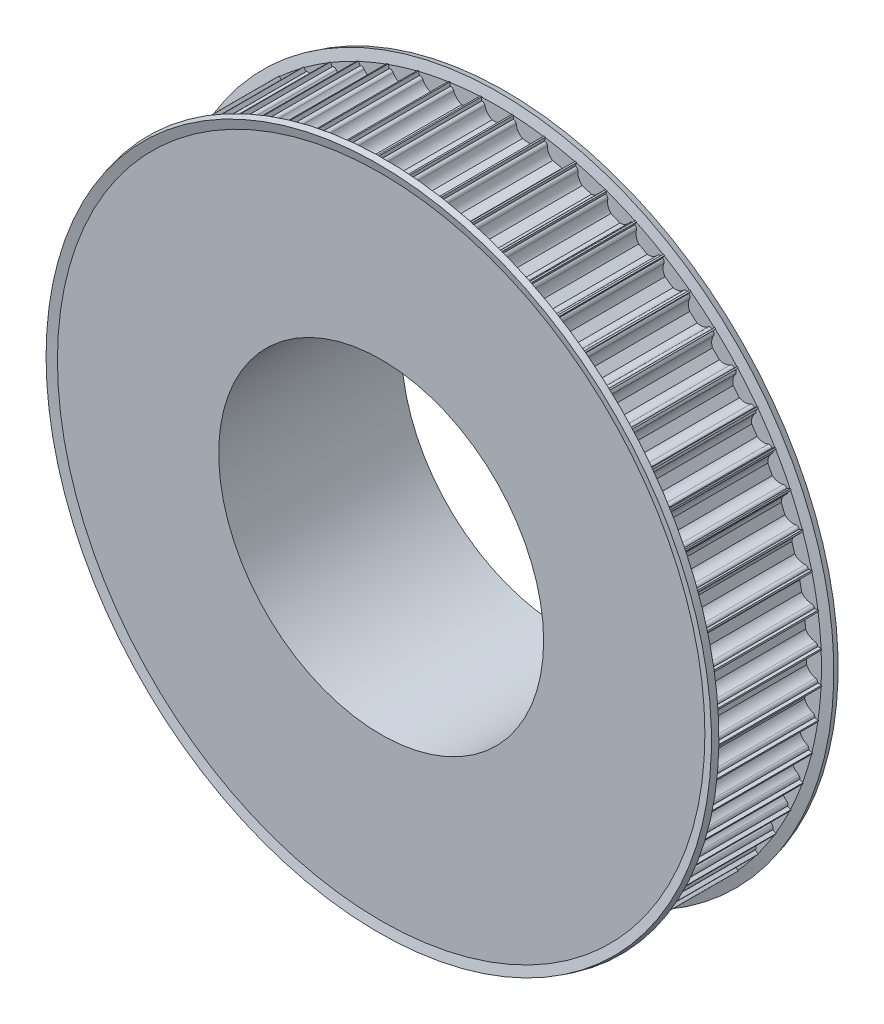
SolidWorks part; units mm, degrees
ref_plane "Front Plane" through (0, 0, 0) normal (0, 0, 1) x (1, 0, 0)
ref_plane "Top Plane" through (0, 0, 0) normal (0, 1, 0) x (1, 0, 0)
ref_plane "Right Plane" through (0, 0, 0) normal (1, 0, 0) x (0, 0, -1)
sketch "Sketch1" plane through (0, 0, 0) normal (1, 0, 0) x (0, 0, -1)
  line L0 (0, 40) -> (45, 40)
  line L1 (45, 40) -> (45, 55.5)
  line L2 (45, 55.5) -> (30, 55.5)
  line L3 (30, 55.5) -> (30, 80)
  line L4 (30, 80) -> (0, 80)
  line L5 (0, 80) -> (0, 40)
  line L6 (0, 0) -> (50000, 0) construction
  dimension "D1" = 30
  dimension "D2" = 40
  dimension "D3" = 15
  dimension "D4" = 40
  dimension "D5" = 15.5
revolve "Revolve1" add sketch "Sketch1" angle 360 about L6
sketch "Sketch2" plane through (0, 0, 0) normal (0, 0, 1) x (1, 0, 0)
  line L1 (3.75, 79) -> (3.6742, 79)
  line L2 (3.75, 79) -> (3.75, 81)
  line L3 (3.75, 81) -> (-3.75, 81)
  line L4 (-3.75, 79) -> (-3.75, 81)
  line L5 (-3.6742, 79) -> (-3.75, 79)
  line L6 (-1.199, 76.25) -> (1.199, 76.25)
  arc A0 (2.9394, 78.4) -> (1.199, 76.25) centre (0, 79) cw
  arc A1 (2.9394, 78.4) -> (3.6742, 79) centre (3.6742, 78.25) cw
  arc A2 (-2.9394, 78.4) -> (-3.6742, 79) centre (-3.6742, 78.25) ccw
  arc A3 (-1.199, 76.25) -> (-2.9394, 78.4) centre (0, 79) cw
  point P11 (3, 79)
  point P14 (-3, 79)
  dimension "D1" = 2
  dimension "D2" = 3
  dimension "D5" = 0.75
  dimension "D3" = 7.5
  dimension "D4" = 79
  dimension "D6" = 2.75
extrude "Cut-Extrude1" cut sketch "Sketch2" against normal blind 35
sketch "Sketch3" plane through (0, 0, 0) normal (0, 0, 1) x (1, 0, 0)
  point P0 (0, 0)
ref_axis "Axis1" through (0, 0, 0) along (0, 0, 1)
pattern_circular "CirPattern1" count 64 over 360 about axis through (0, 0, 0) along (0, 0, 1) of "Cut-Extrude1"
sketch "Sketch4" plane through (0, 0, 0) normal (1, 0, 0) x (0, 0, -1)
  line L3 (0, 79.8948) -> (1.5, 79.8948)
  line L8 (1.5, 79.8948) -> (0.0511, 79.5066)
  line L9 (1.5, 79.8948) -> (0.8569, 82.2948)
  line L10 (0.0511, 79.5066) -> (-0.592, 81.9066)
  line L11 (0.8569, 82.2948) -> (-0.592, 81.9066)
  line L14 (22.1322, 25.0648) -> (22.1322, -29.3474) construction
  line L15 (1.5, 79.8948) -> (0, 79.8948)
  line L16 (1.5, 79.8948) -> (1.5, 74.8948)
  line L17 (1.5, 74.8948) -> (0, 74.8948)
  line L18 (0, 79.8948) -> (0, 74.8948)
  line L19 (30, -73.3147) -> (0, -73.3147)
  line L20 (15, 79.8948) -> (15, 40.4807) construction
  line L21 (0, 79.8948) -> (30, 79.8948) construction
  line L22 (0, -75.8774) -> (30, -75.8774)
  line L23 (0, -73.3147) -> (0, -75.8774)
  line L24 (30, -73.3147) -> (0, -73.3147)
  line L25 (30, -75.8774) -> (30, -73.3147)
  line L27 (0, -73.3147) -> (0, -75.8774)
  line L28 (30, -73.3147) -> (0, -73.3147)
  line L29 (30, -75.8774) -> (30, -73.3147)
  line L30 (30, 40.4807) -> (0, 40.4807) construction
  line L38 (30, 79.8948) -> (30, 74.8948)
  line L39 (28.5, 74.8948) -> (30, 74.8948)
  line L40 (0, -75.8774) -> (30, -75.8774)
  line L41 (28.5, 79.8948) -> (28.5, 74.8948)
  line L42 (28.5, 79.8948) -> (30, 79.8948)
  line L43 (29.1431, 82.2948) -> (30.592, 81.9066)
  line L44 (29.9489, 79.5066) -> (30.592, 81.9066)
  line L45 (28.5, 79.8948) -> (29.1431, 82.2948)
  line L46 (28.5, 79.8948) -> (29.9489, 79.5066)
  line L47 (30, 79.8948) -> (28.5, 79.8948)
  dimension "D1" = 1.5
  dimension "D3" = 1.5
  dimension "D4" = 165
  dimension "D5" = 2.4
  dimension "D6" = 0
revolve "Revolve3" add sketch "Sketch4" angle 360 about axis through (0, 0, 0) along (0, 0, 1) region at (0, 80.9988, -0.4493) region at (0, 79.7643, -0.5085) region at (0, 77.2974, -0.7599) region at (0, -74.5961, -15) region at (0, 77.2974, -29.2401)
